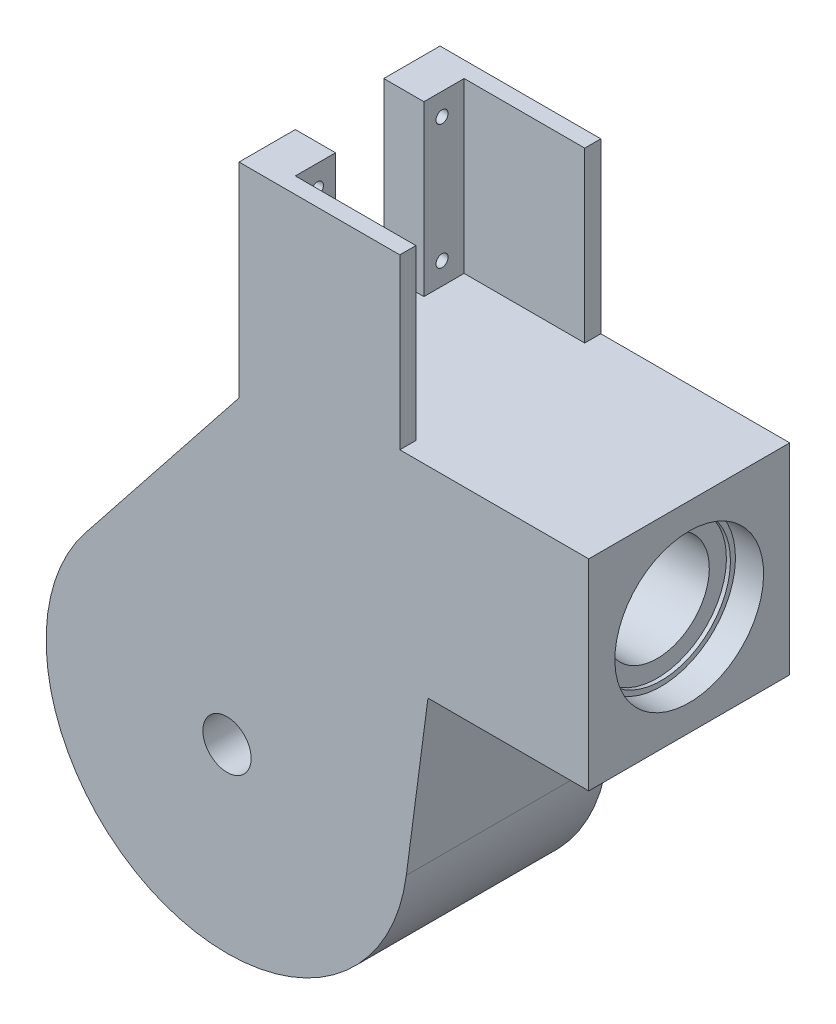
SolidWorks part; units mm, degrees
ref_plane "Front Plane" through (0, 0, 0) normal (0, 0, 1) x (1, 0, 0)
ref_plane "Top Plane" through (0, 0, 0) normal (0, 1, 0) x (1, 0, 0)
ref_plane "Right Plane" through (0, 0, 0) normal (1, 0, 0) x (0, 0, -1)
sketch "Sketch1" plane through (0, 0, 0) normal (0, 0, 1) x (1, 0, 0)
  line L0 (50, 35) -> (44.6145, -5.8778)
  line L1 (90, 85) -> (50, 85)
  line L2 (90, 85) -> (90, 35)
  line L3 (90, 35) -> (50, 35)
  line L4 (50, 85) -> (50, 35)
  line L5 (90, 85) -> (50, 35) construction
  line L6 (90, 35) -> (50, 85) construction
  line L7 (50, 85) -> (10, 85)
  line L8 (10, 85) -> (-35.2511, 27.9707)
  circle A0 centre (0, 0) radius 45
  point P3 (70, 60)
  dimension "D1" = 90
  dimension "D2" = 70
  dimension "D3" = 40
  dimension "D4" = 50
  dimension "D5" = 60
  dimension "D6" = 40
extrude "Boss-Extrude1" add sketch "Sketch1" along normal blind 50 contours L1 L4 L3 L2 | A0 L0 L4 L7 L8 | A0 region at (70, 60, 0) region at (23.7004, 56.6095, 0) region at (0, 0, 0)
sketch "Sketch3" plane through (90, 0, 0) normal (1, 0, 0) x (0, 0, -1)
  line L0 (-50, 85) -> (0, 35) construction
  line L1 (0, 35) -> (0, 85) construction
  line L2 (0, 85) -> (-50, 35) construction
  line L3 (-50, 85) -> (-50, 35) construction
  line L4 (-50, 35) -> (0, 35) construction
  circle A0 centre (-25, 60) radius 13
  dimension "D1" = 26
extrude "Cut-Extrude1" cut sketch "Sketch3" against normal blind 130
ref_plane "Plane1" through (-40, 0, 0) normal (-1, 0, 0) x (0, 0, 1)
sketch "Sketch6" plane through (0, 85, 0) normal (0, 1, 0) x (1, 0, 0)
  line L0 (90, 0) -> (10, 0) construction
  line L18 (43, 0) -> (3, 0)
  line L19 (43, 0) -> (43, -4)
  line L20 (43, -4) -> (3, -4)
  line L21 (3, 0) -> (3, -4)
  line L22 (90, -50) -> (10, -50) construction
  line L23 (43, -50) -> (3, -50)
  line L24 (43, -50) -> (43, -46)
  line L25 (43, -46) -> (3, -46)
  line L26 (3, -50) -> (3, -46)
  line L27 (13, -14) -> (13, -36) construction
  line L28 (3, -46) -> (13, -46)
  line L29 (3, -46) -> (3, -36)
  line L30 (3, -36) -> (13, -36)
  line L31 (13, -46) -> (13, -36)
  line L32 (3, -4) -> (13, -4)
  line L33 (3, -4) -> (3, -14)
  line L34 (3, -14) -> (13, -14)
  line L35 (13, -4) -> (13, -14)
  line L36 (13, -25) -> (-8, -25) construction
  line M15 (90, 0) -> (10, 0)
  line M16 (10, 0) -> (10, -50)
  line M17 (10, -50) -> (90, -50)
  dimension "D1" = 42
  dimension "D2" = 4
  dimension "D3" = 22
  dimension "D4" = 10
  dimension "D5" = 3
  dimension "D6" = 10
  dimension "D7" = 30
extrude "Boss-Extrude3" add sketch "Sketch6" along normal blind 42 and the other way blind 10 contours L20 L19 M15 M16 | L18 L21 L20 M16 | L33 L34 L20 M16 | L35 L20 L34 M16 | L25 L31 L30 M16 | L30 L29 L25 M16 | L26 L23 L25 M16 | L24 L25 M16 M17 region at (26.5, 85, 2) region at (11.5, 85, 41) region at (6.5, 85, 41) region at (6.5, 85, 2) region at (6.5, 85, 9) region at (11.5, 85, 9) region at (6.5, 85, 48) region at (26.5, 85, 48)
sketch "Sketch5" plane through (-40, 0, 0) normal (-1, 0, 0) x (0, 0, 1)
  line L1 (46, 40) -> (4, 40)
  line L2 (46, 40) -> (46, 80)
  line L3 (46, 80) -> (4, 80)
  line L4 (4, 40) -> (4, 80)
  line L5 (46, 40) -> (4, 80) construction
  line L6 (46, 80) -> (4, 40) construction
  point P0 (25, 60)
  dimension "D1" = 42
  dimension "D2" = 40
extrude "Cut-Extrude2" cut sketch "Sketch5" against normal up to surface (43 mm away) and the other way blind 11 up to face at (3, 101.589, 7)
sketch "Sketch9" plane through (13, 0, 0) normal (1, 0, 0) x (0, 0, -1)
  line L0 (-46, 127) -> (-4, 85) construction
  line L2 (-4, 127) -> (-46, 85) construction
  arc A0 (-39.4035, 122.5235) -> (-41.5235, 120.4035) centre (-25, 106) ccw
  circle A1 centre (-9.5002, 121.4998) radius 1.5
  circle A2 centre (-9.5002, 90.5002) radius 1.5
  circle A3 centre (-40.4998, 90.5002) radius 1.5
  circle A4 centre (-40.4998, 121.4998) radius 1.5
  arc A5 (-41.5235, 91.5965) -> (-39.4035, 89.4765) centre (-25, 106) ccw
  arc A6 (-10.5965, 89.4765) -> (-8.4765, 91.5965) centre (-25, 106) ccw
  arc A8 (-8.4765, 120.4035) -> (-10.5965, 122.5235) centre (-25, 106) ccw
  point P20 (-25, 106)
  dimension "D1" = 4
extrude "Cut-Extrude4" cut sketch "Sketch9" against normal blind 10 contours A0 A4 | A0 A4 | A0 A1 | A0 A1 | A0 A2 | A0 A2 | A0 A3 | A0 A3 region at (13, 121.0431, 40.0431) region at (13, 121.9433, 40.9433) region at (13, 121.9433, 9.0567) region at (13, 121.0431, 9.9569) region at (13, 90.0567, 9.0567) region at (13, 90.9569, 9.9569) region at (13, 90.9569, 40.0431) region at (13, 90.0567, 40.9433)
sketch "Skizze1" plane through (0, 0, 0) normal (0, 0, -1) x (-1, 0, 0)
  circle A0 centre (0, 0) radius 6
  dimension "D1" = 12
extrude "Schnitt-Linear austragen1" cut sketch "Skizze1" against normal up to surface (50 mm away) up to face at (34.3469, 59.9769, 50)
sketch "Skizze2" plane through (0, 0, 0) normal (0, 0, -1) x (-1, 0, 0)
  circle A0 centre (0, 0) radius 6
  circle A1 centre (0, 0) radius 17.5
  circle A2 centre (0, 0) radius 6 construction
  dimension "D1" = 35
extrude "Aufsatz-Linear austragen1" add sketch "Skizze2" along normal blind 36
sketch "Skizze3" plane through (0, 0, 0) normal (0, 0, -1) x (-1, 0, 0)
  circle A0 centre (0, 0) radius 17.5
  circle A1 centre (0, 0) radius 21.5
  circle A2 centre (0, 0) radius 17.5 construction
  dimension "D1" = 43
extrude "Aufsatz-Linear austragen2" add sketch "Skizze3" along normal blind 1
sketch "Skizze4" plane through (0, 0, -36) normal (0, 0, -1) x (-1, 0, 0)
  line L0 (-6, 0) -> (-17.5, 0) construction
  circle A0 centre (0, 0) radius 6 construction
  circle A1 centre (0, 0) radius 17.5 construction
  circle A2 centre (-11.75, 0) radius 1.65
  circle A3 centre (-5.875, 10.1758) radius 1.65
  circle A4 centre (5.875, 10.1758) radius 1.65
  circle A5 centre (11.75, 0) radius 1.65
  circle A6 centre (5.875, -10.1758) radius 1.65
  circle A7 centre (-5.875, -10.1758) radius 1.65
  point P21 (0, 0)
  dimension "D1" = 6
extrude "Schnitt-Linear austragen2" cut sketch "Skizze4" against normal blind 15
sketch "Skizze5" plane through (90, 0, 0) normal (1, 0, 0) x (0, 0, -1)
  circle A0 centre (-25, 60) radius 18.5
  dimension "D1" = 37
extrude "Schnitt-Linear austragen3" cut sketch "Skizze5" against normal blind 7
sketch "Skizze6" plane through (83, 0, 0) normal (1, 0, 0) x (0, 0, -1)
  circle A0 centre (-25, 60) radius 17.25
  dimension "D1" = 34.5
extrude "Schnitt-Linear austragen4" cut sketch "Skizze6" against normal blind 1
ref_plane "Ebene1" through (46.5, 0, 0) normal (1, 0, 0) x (0, 0, -1)
mirror "Spiegeln1" about plane through (46.5, 0, 0) normal (1, 0, 0) of "Schnitt-Linear austragen4", "Schnitt-Linear austragen3"
